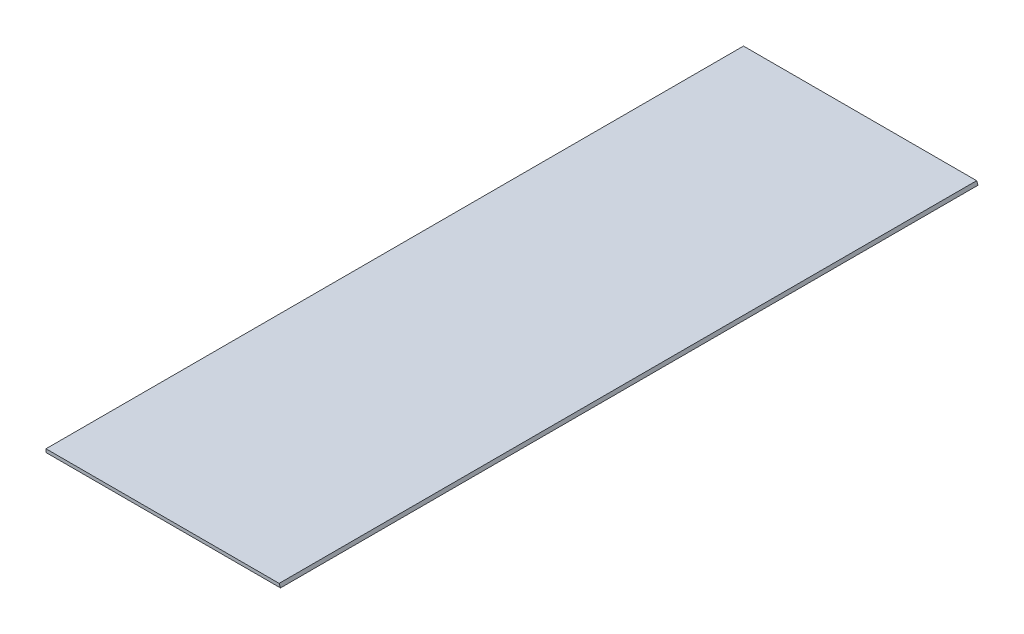
SolidWorks part; units mm, degrees
ref_plane "Front Plane" through (0, 0, 0) normal (0, 0, 1) x (1, 0, 0)
ref_plane "Top Plane" through (0, 0, 0) normal (0, 1, 0) x (1, 0, 0)
ref_plane "Right Plane" through (0, 0, 0) normal (1, 0, 0) x (0, 0, -1)
sketch "Sketch1" plane through (0, 0, 0) normal (0, 0, 1) x (1, 0, 0)
  line L0 (0, 0) -> (0, 2.3622)
  line L1 (0, 2.3622) -> (167.6775, 2.3622)
  line L2 (167.6775, 2.3622) -> (168.656, 0)
  line L3 (168.656, 0) -> (0, 0)
  dimension "D1" = 2.3622
  dimension "D2" = 168.656
  dimension "D3" = 67.5
extrude "Boss-Extrude1" add sketch "Sketch1" along normal blind 501.65
